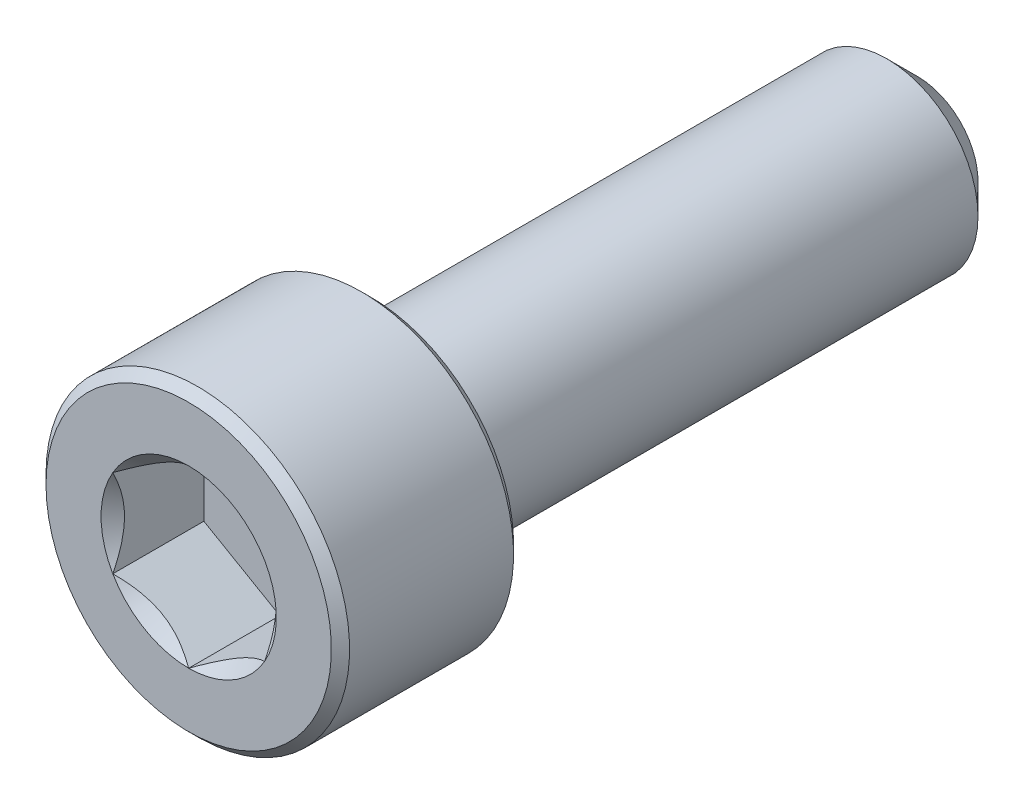
SolidWorks part; units mm, degrees
ref_plane "Front Plane" through (0, 0, 0) normal (0, 0, 1) x (1, 0, 0)
ref_plane "Top Plane" through (0, 0, 0) normal (0, 1, 0) x (1, 0, 0)
ref_plane "Right Plane" through (0, 0, 0) normal (1, 0, 0) x (0, 0, -1)
sketch "Sketch1" plane through (0, 0, 0) normal (1, 0, 0) x (0, 0, -1)
  line L0 (-12, 0) -> (12, 0) construction
  line L1 (12, 0) -> (12, 2) construction
  line L2 (12, 2) -> (11, 3) construction
  line L3 (11, 3) -> (-6, 3) construction
  line L5 (-6, 3) -> (-6, 5) construction
  line L6 (-6, 5) -> (-12, 5) construction
  line L7 (-12, 5) -> (-12, 0) construction
  line L8 (12, 2) -> (12, 3) construction
  line L9 (11.9375, 3.1083) -> (12.4375, 2.2422) construction
  line L10 (12.4375, 2.2422) -> (12.9375, 3.1083) construction
  line L11 (12.9375, 3.1083) -> (11.9375, 3.1083) construction
  line L12 (12.4375, 3.1083) -> (12.4375, 3) construction
  line L13 (12.4375, 2.2422) -> (12.4375, 2.3505) construction
  line L14 (12.375, 2.3505) -> (12.5, 2.3505) construction
  line L15 (12, 3) -> (12.875, 3) construction
  line L16 (11.9687, 3.0541) -> (12.9062, 3.0541) construction
  line L17 (12, 0) -> (12, -3) construction
  line L18 (-6.3, 5) -> (-6, 4.7) construction
  line L19 (-11.7, 5) -> (-12, 4.7) construction
  point P0 (-12, 2.5)
  point P3 (8.5, 3)
  point P4 (0, 0)
  point P22 (12.4375, 2.3505)
  point P24 (-6, 3)
  point P25 (12.4375, 3)
  point P28 (12.4375, 3.0541)
  point P29 (8.5, -3)
  point P31 (-9, 5)
  point P37 (-7.05, 5)
  point P38 (-11.55, 5)
  point P41 (-9, 0)
  dimension "head height" = 6
  dimension "D1" = 45
  dimension "Head Diameter" = 10
  dimension "Thread Size" = 6
  dimension "drive size" = 5
  dimension "Thread Pitch" = 1
  dimension "D2" = 0.125
  dimension "D3" = 1
  dimension "D4" = 3.5
  dimension "D7" = 0.3
  dimension "D8" = 0.3
  dimension "D9" = 0.3
  dimension "D10" = 0.15
  dimension "D11" = 0.75
  dimension "length" = 18
  dimension "Drive Depth" = 3
sketch "Sketch2" plane through (0, 0, 0) normal (1, 0, 0) x (0, 0, -1)
  line L1 (-11.7, 5) -> (-6.3, 5)
  line L4 (11, 3) -> (12, 2)
  line L5 (12, 2) -> (12, 0)
  line L6 (-6.3, 5) -> (-6, 4.7) construction
  line L7 (12, 0) -> (-12, 0)
  line L8 (-11.7, 5) -> (-12, 4.7) construction
  line L9 (-6.3, 5) -> (-6, 4.7)
  line L10 (-11.7, 5) -> (-12, 4.7)
  line L11 (-12, 4.7) -> (-12, 0)
  line L12 (-6, 4.7) -> (-6, 3)
  line L13 (-6, 3) -> (11, 3)
revolve "Revolve1" add sketch "Sketch2" angle 360 about L7
sketch "Sketch3" plane through (0, 0, 12) normal (0, 0, 1) x (1, 0, 0)
  line L1 (0, 2.8868) -> (-2.5, 1.4434)
  line L2 (-2.5, 1.4434) -> (-2.5, -1.4434)
  line L3 (-2.5, -1.4434) -> (0, -2.8868)
  line L4 (0, -2.8868) -> (2.5, -1.4434)
  line L5 (2.5, -1.4434) -> (2.5, 1.4434)
  line L6 (2.5, 1.4434) -> (0, 2.8868)
  circle A0 centre (0, 0) radius 2.5 construction
  dimension "D1" = 5
extrude "Cut-Extrude1" cut sketch "Sketch3" against normal up to vertex (3 mm away) up to point (0, 0, 9)
sketch "Sketch4" plane through (0, 0, 12) normal (0, 0, 1) x (1, 0, 0)
  circle A0 centre (0, 0) radius 2.8868
extrude "Cut-Extrude2" cut sketch "Sketch4" against normal blind 0.5 draft 45
ref_plane "Plane1" [suppressed] through (0, 0, 6) normal (0, 0, 1) x (1, 0, 0)
split "Split1" [suppressed] bodies to split 106
sketch "Sketch6" [suppressed] plane through (0, 0, -12) normal (0, 0, -1) x (-1, 0, 0)
  circle A0 centre (0, 0) radius 3
curve "Helix/Spiral1" [suppressed] pitch 1 height 19 turns 19
sketch "Sketch7" [suppressed] plane through (0, 0, 0) normal (1, 0, 0) x (0, 0, -1)
  line L0 (11.9687, 3.0541) -> (12.9062, 3.0541)
  line L1 (12.9062, 3.0541) -> (12.5, 2.3505)
  line L2 (12.5, 2.3505) -> (12.375, 2.3505)
  line L3 (12.375, 2.3505) -> (11.9687, 3.0541)
sweep "Cut-Sweep1" [suppressed] cut profiles "Sketch7" path "Helix/Spiral1"
sketch "Sketch8" [suppressed] plane through (0, 0, 6) normal (0, 0, -1) x (-1, 0, 0)
  circle A0 centre (0, 0) radius 3
extrude "Boss-Extrude1" [suppressed] add sketch "Sketch8" along normal through all draft 45
ref_plane "Plane2" [suppressed] through (0, 0, 9) normal (0, 0, 1) x (1, 0, 0)
sketch "Sketch9" [suppressed] plane through (0, 0, 9) normal (0, 0, 1) x (1, 0, 0)
  line L0 (0, 4.8625) -> (0.1309, 4.9983)
  line L1 (0, 4.8625) -> (-0.1309, 4.9983)
  line L2 (0, 5) -> (0, 0) construction
  line L3 (-0.1309, 4.9983) -> (0, 0) construction
  line L4 (0, 0) -> (0.1309, 4.9983) construction
  arc A0 (0.1309, 4.9983) -> (-0.1309, 4.9983) centre (0, 0) ccw
  circle A1 centre (0, 0) radius 4.8625 construction
  dimension "D2" = 9.725
  dimension "D3" = 3
extrude "Cut-Extrude4" [suppressed] cut sketch "Sketch9" against normal up to vertex and the other way up to vertex
pattern_circular "CirPattern2" [suppressed] count 96 over 360 about axis through (0, 0, 12) along (0, 0, -1) of bodies 113
equation "\"D2@Sketch1\" = \"Thread Pitch@Sketch1\" / 8"
equation "\"D3@Sketch1\" = \"Thread Pitch@Sketch1\""
equation "\"D3@Helix/Spiral1\" = \"length@Sketch1\" + \"Thread Pitch@Sketch1\""
equation "\"D4@Helix/Spiral1\" = \"Thread Pitch@Sketch1\""
equation "\"D4@Sketch1\" = \"Thread Pitch@Sketch1\" * 3.5"
equation "\"D7@Sketch1\"=\"head height@Sketch1\"*.05"
equation "\"D8@Sketch1\"=\"D7@Sketch1\""
equation "\"D9@Sketch1\"=\"D7@Sketch1\""
equation "\"D10@Sketch1\"=\"D7@Sketch1\"/2"
equation "\"D11@Sketch1\"=\"D10@Sketch1\"*5"
equation "\"D1@CirPattern2\"=( 360 / \"D3@Sketch9\" )*0.8"
equation "\"D1@Sketch3\" = \"drive size@Sketch1\""
equation "\"D2@Sketch9\"=\"Head Diameter@Sketch1\" * 0.9725"
